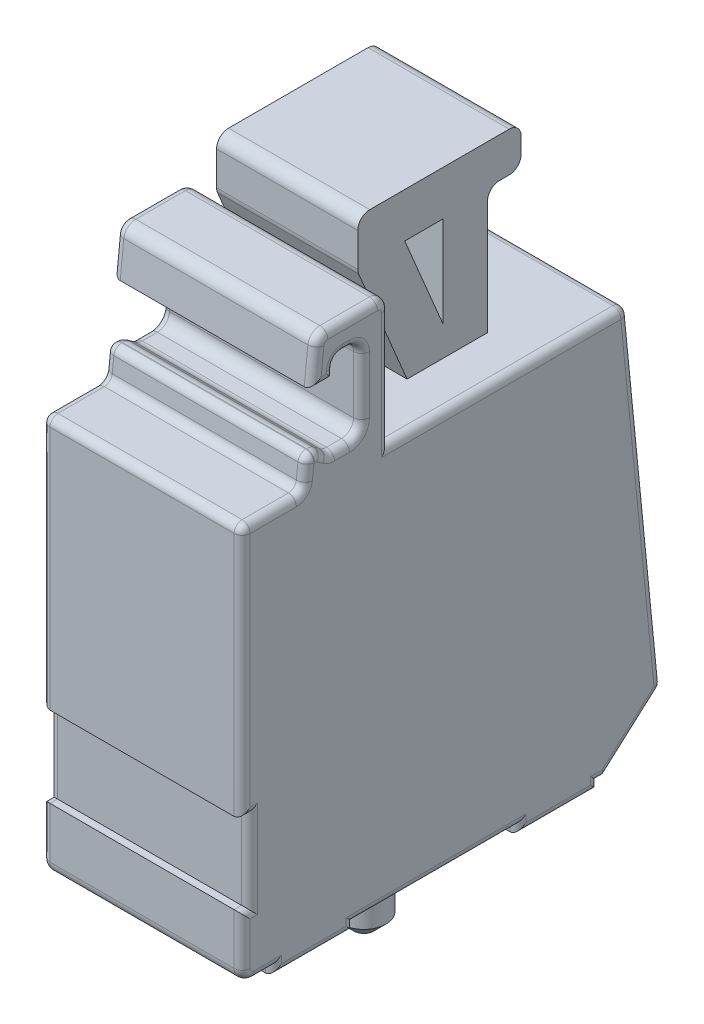
SolidWorks part; units mm, degrees
ref_plane "Front" through (0, 0, 0) normal (0, 0, 1) x (1, 0, 0)
ref_plane "Top" through (0, 0, 0) normal (0, 1, 0) x (1, 0, 0)
ref_plane "Right" through (0, 0, 0) normal (1, 0, 0) x (0, 0, -1)
sketch "Sketch1" plane through (0, 0, 0) normal (1, 0, 0) x (0, 0, -1)
  line L0 (0.7807, 0) -> (2.7981, 0)
  line L1 (2.7981, 0) -> (2.7981, 0.1867)
  line L2 (2.7981, 0.1867) -> (6.8903, 0.1867)
  line L3 (6.8903, 0.1867) -> (6.8903, 0)
  line L4 (6.8903, 0) -> (8.9077, 0)
  line L5 (8.9077, 0) -> (8.9077, 0.1867)
  line L6 (8.9077, 0.1867) -> (9.0688, 0.1867)
  line L7 (9.0688, 0.1867) -> (10.5, 1.4603)
  line L8 (10.5, 1.4603) -> (9.6442, 10.1)
  line L9 (9.6442, 10.1) -> (7.3103, 10.1)
  line L10 (7.3103, 10.1) -> (7.3103, 12.9414)
  line L11 (7.6103, 13.2414) -> (7.853, 13.2414)
  line L12 (8.153, 13.5414) -> (8.153, 13.9334)
  line L13 (7.853, 14.2334) -> (4.3692, 14.2334)
  line L14 (4.0692, 13.9334) -> (4.0692, 13.0926)
  line L15 (4.0927, 12.9763) -> (5.3021, 10.1)
  line L16 (5.3021, 10.1) -> (3.6803, 10.1)
  line L17 (3.6803, 10.1) -> (3.6803, 13.0297)
  line L18 (3.3803, 13.3297) -> (2.1404, 13.3297)
  line L19 (1.842, 13.0605) -> (1.7528, 12.1969)
  line L20 (1.7528, 12.1969) -> (2.3065, 12.1969)
  line L21 (2.3065, 12.1969) -> (2.3065, 12.6465)
  line L22 (2.3065, 12.6465) -> (2.6817, 12.6465)
  line L23 (2.9817, 12.3465) -> (2.9817, 10.9136)
  line L25 (1.6117, 10.8304) -> (1.5362, 10.1)
  line L26 (1.5362, 10.1) -> (0, 10.1)
  line L27 (0, 10.1) -> (0, 3.777)
  line L28 (0, 3.777) -> (0.1867, 3.777)
  line L29 (0.1867, 3.777) -> (0.1867, 1.7596)
  line L30 (0.1867, 1.7596) -> (0, 1.7596)
  line L31 (0, 1.7596) -> (0, 0.4867)
  line L32 (0.3, 0.1867) -> (0.7807, 0.1867)
  line L33 (0.7807, 0.1867) -> (0.7807, 0)
  line L34 (0.1867, 3.777) -> (0.1867, 5.2453) construction
  line L35 (0.1867, 5.2453) -> (0, 5.2453) construction
  line L36 (0.7807, 0.1867) -> (1.7894, 0.1867) construction
  line L37 (1.7894, 0.1867) -> (1.7894, 0) construction
  line L38 (1.6117, 10.8304) -> (1.8112, 10.8304)
  line L39 (1.9852, 10.7747) -> (2.1333, 10.6693)
  line L40 (2.3073, 10.6136) -> (2.6817, 10.6136)
  arc A0 (0, 0.4867) -> (0.3, 0.1867) centre (0.3, 0.4867) ccw
  arc A1 (4.0692, 13.0926) -> (4.0927, 12.9763) centre (4.3692, 13.0926) ccw
  arc A2 (4.3692, 14.2334) -> (4.0692, 13.9334) centre (4.3692, 13.9334) ccw
  arc A3 (7.3103, 12.9414) -> (7.6103, 13.2414) centre (7.6103, 12.9414) cw
  arc A4 (7.853, 13.2414) -> (8.153, 13.5414) centre (7.853, 13.5414) ccw
  arc A5 (8.153, 13.9334) -> (7.853, 14.2334) centre (7.853, 13.9334) ccw
  arc A6 (1.8112, 10.8304) -> (1.9852, 10.7747) centre (1.8112, 10.5304) cw
  arc A7 (2.1333, 10.6693) -> (2.3073, 10.6136) centre (2.3073, 10.9136) ccw
  arc A8 (2.9817, 10.9136) -> (2.6817, 10.6136) centre (2.6817, 10.9136) cw
  arc A9 (2.6817, 12.6465) -> (2.9817, 12.3465) centre (2.6817, 12.3465) cw
  arc A10 (2.1404, 13.3297) -> (1.842, 13.0605) centre (2.1404, 13.0297) ccw
  arc A11 (3.6803, 13.0297) -> (3.3803, 13.3297) centre (3.3803, 13.0297) ccw
  point P65 (0, 0)
  dimension "D3" = 0.3
  dimension "D1" = 10.1
  dimension "D2" = 10.5
extrude "Boss-Extrude1" add sketch "Sketch1" along normal blind 5
sketch "Sketch2" plane through (0, 0, -7.3103) normal (0, 0, -1) x (-1, 0, 0)
  line L0 (-2.0559, 12.9414) -> (-2.0559, 10.1) construction
  line L1 (-5, 12.9414) -> (0, 12.9414) construction
  line L2 (-5, 10.1) -> (0, 10.1) construction
  line L3 (-0.2921, 10.1) -> (2.2848, 10.1)
  line L5 (-3.8197, 14.2356) -> (-3.8197, 10.1)
  line L7 (-0.2921, 14.2356) -> (-0.2921, 10.1)
  line L8 (-3.8197, 14.2356) -> (-0.2921, 10.1) construction
  line L9 (-3.8197, 10.1) -> (-0.2921, 14.2356) construction
  line L10 (-6.3967, 14.2356) -> (-3.8197, 14.2356)
  line L11 (-6.3967, 14.2356) -> (-6.3967, 10.1)
  line L12 (-6.3967, 10.1) -> (-3.8197, 10.1)
  line L13 (2.2848, 14.2356) -> (2.2848, 10.1)
  line L14 (-6.3967, 14.2356) -> (2.2848, 10.1) construction
  line L15 (-6.3967, 10.1) -> (2.2848, 14.2356) construction
  line L16 (-0.2921, 14.2356) -> (2.2848, 14.2356)
  point P6 (-2.0559, 12.1678)
  point P11 (-2.0559, 12.1678)
extrude "Cut-Extrude1" cut sketch "Sketch2" against normal up to surface and the other way through all up to face at (2.5, 11.5381, -4.6974)
ref_plane "Plane1" through (2.0559, 0, 0) normal (1, 0, 0) x (0, 0, -1)
sketch "Sketch4" plane through (3.8197, 0, 0) normal (1, 0, 0) x (0, 0, -1)
  line L0 (5.2431, 13.1179) -> (6.1948, 10.8545)
  line L1 (6.1948, 10.8545) -> (6.1948, 13.1179)
  line L2 (6.1948, 13.1179) -> (5.2431, 13.1179)
  line L4 (4.0927, 12.9763) -> (5.3021, 10.1) construction
  line L5 (7.3103, 12.9414) -> (7.3103, 10.1) construction
  line L6 (5.7189, 11.9862) -> (4.6974, 11.5381) construction
  line L7 (6.1948, 12.2755) -> (7.3103, 12.2755) construction
  line L8 (6.2083, 13.1179) -> (6.2083, 14.2334) construction
  line L9 (4.3692, 14.2334) -> (7.853, 14.2334) construction
  point P15 (6.1948, 12.2755)
extrude "Cut-Extrude2" cut sketch "Sketch4" against normal blind 1
mirror "Mirror1" about plane through (2.0559, 0, 0) normal (1, 0, 0) of "Cut-Extrude2"
sketch "Sketch5" plane through (0, 0.5233, -10.5928) normal (0, -0.0986, 0.9951) x (1, 0, 0)
  line L0 (2.0879, -0.3547) -> (2.0879, 9.6235) construction
  line L1 (5, -0.3547) -> (0, -0.3547) construction
  line L2 (5, 9.6235) -> (0, 9.6235) construction
  circle A0 centre (2.0879, 6.1131) radius 1.5711
  circle A1 centre (2.0879, 2.6835) radius 0.4239
  point P10 (2.0879, 6.1131)
extrude "Cut-Extrude3" cut sketch "Sketch5" along normal blind 2
sketch "Sketch6" plane through (0, 0.847, -8.551) normal (0, 0.0986, -0.9951) x (-1, 0, 0)
  line L1 (-2.5892, 6.1319) -> (-1.4417, 6.1319)
  line L2 (-2.5892, 6.1319) -> (-2.5892, 4.886)
  line L3 (-2.5892, 4.886) -> (-1.4417, 4.886)
  line L4 (-1.4417, 6.1319) -> (-1.4417, 4.886)
  line L5 (-2.5892, 6.1319) -> (-1.4417, 4.886) construction
  line L6 (-2.5892, 4.886) -> (-1.4417, 6.1319) construction
  point P0 (-2.0154, 5.509)
extrude "Cut-Extrude4" cut sketch "Sketch6" against normal blind 2
chamfer "Chamfer1" distance 1 angle 45 1 edges at (2.0879, 4.846, -8.1548)
fillet "Fillet1" radius 0.2 80 edges at (0, 11.5648, -3.6803) (0, 13.2418, -3.5924) (0, 13.3297, -2.7603) (0, 13.2524, -1.9395) (0, 12.6287, -1.7974) (0, 12.1969, -2.0297) (0, 12.4217, -2.3065) (0, 12.6465, -2.4941) (0, 12.5586, -2.8938) (0, 11.6301, -2.9817) (0, 10.7015, -2.8938) (0, 10.6136, -2.4945) (0, 10.6279, -2.216) (0, 10.722, -2.0593) (0, 10.8161, -1.9026) (0, 10.8304, -1.7114) (0, 10.4652, -1.574) (0, 10.1, -0.7681) (0, 6.9385, 0) (0, 3.777, -0.0934) (0, 2.7683, -0.1867) (0, 1.7596, -0.0934) (0, 1.1232, 0) (0, 0.2746, -0.0879) (0, 0.1867, -0.5403) (0, 0.0934, -0.7807) (0, 0, -1.7894) (0, 0.0934, -2.7981) (0, 0.1867, -4.8442) (0, 0.0934, -6.8903) (0, 0, -7.899) (0, 0.0934, -8.9077) (0, 0.1867, -8.9883) (0, 0.8235, -9.7844) (0, 5.7802, -10.0721) (0, 10.1, -6.6622) (5, 5.7802, -10.0721) (5, 0.8235, -9.7844) (5, 0.1867, -8.9883) (5, 0.0934, -8.9077) (5, 0, -7.899) (5, 0.0934, -6.8903) (5, 0.1867, -4.8442) (5, 0.0934, -2.7981) (5, 0, -1.7894) (5, 0.0934, -0.7807) (5, 0.1867, -0.5403) (5, 0.2746, -0.0879) (5, 1.1232, 0) (5, 1.7596, -0.0934) (5, 2.7683, -0.1867) (5, 3.777, -0.0934) (5, 6.9385, 0) (5, 10.1, -0.7681) (5, 10.4652, -1.574) (5, 10.8304, -1.7114) (5, 10.8161, -1.9026) (5, 10.722, -2.0593) (5, 10.6279, -2.216) (5, 10.6136, -2.4945) (5, 10.7015, -2.8938) (5, 11.6301, -2.9817) (5, 12.5586, -2.8938) (5, 12.6465, -2.4941) (5, 12.4217, -2.3065) (5, 12.1969, -2.0297) (5, 12.6287, -1.7974) (5, 13.2524, -1.9395) (5, 13.3297, -2.7603) (5, 13.2418, -3.5924) (5, 11.5648, -3.6803) (5, 10.1, -6.6622) (2.5, 12.6465, -2.3065) (2.5, 10.8304, -1.6117) (2.5, 10.1, -1.5362) (2.5, 10.1, 0) (2.5, 1.4603, -10.5) (2.0879, 5.0432, -10.1451) (2.0879, 2.7719, -10.3701) (2.5, 10.1, -9.6442)
sketch "Sketch7" plane through (0, 0.1867, 0) normal (0, -1, 0) x (1, 0, 0)
  line L0 (2.5, -9.0688) -> (2.5, -4.7639) construction
  line L1 (4.8, -9.0688) -> (0.2, -9.0688) construction
  line L2 (4.8, -8.9077) -> (0.2, -8.9077) construction
  line L3 (4.3246, -0.6201) -> (0.6754, -0.6201)
  line L4 (4.3246, -0.6201) -> (4.3246, -8.9077)
  line L5 (4.3246, -8.9077) -> (0.6754, -8.9077)
  line L6 (0.6754, -0.6201) -> (0.6754, -8.9077)
  line L7 (4.3246, -0.6201) -> (0.6754, -8.9077) construction
  line L8 (4.3246, -8.9077) -> (0.6754, -0.6201) construction
extrude "Cut-Extrude5" cut sketch "Sketch7" along normal through all
sketch "Sketch8" plane through (0, 0, 0) normal (0, -1, 0) x (1, 0, 0)
  line L0 (2.5, -5.5409) -> (2.5, -11.1188) construction
  line L1 (0.2, -10.4909) -> (4.8, -10.4909) construction
  line L3 (0, -7.0903) -> (0, -2.5981) construction
  circle A0 centre (2.5, -5.5409) radius 0.55
  point P5 (2.7751, -5.5409)
  dimension "D2" = 1.1
  dimension "D1" = 4.95
  dimension "D3" = 2.5
extrude "Boss-Extrude2" add sketch "Sketch8" along normal blind 2.5 and the other way up to surface (0.1867 mm away) separate body other way up to face at (2.5, 0.1867, -4.8122)
chamfer "Chamfer2" distance 0.3 angle 45 1 edges at (2.5, -2.5, -6.0909)
ref_axis "Axis1" through (2.5, 0.1867, -5.5409) along (0, -1, 0)
ref_plane "Plane2" through (0, 0, 0) normal (0, -1, 0) x (-1, 0, 0)
ref_point "Point1"
